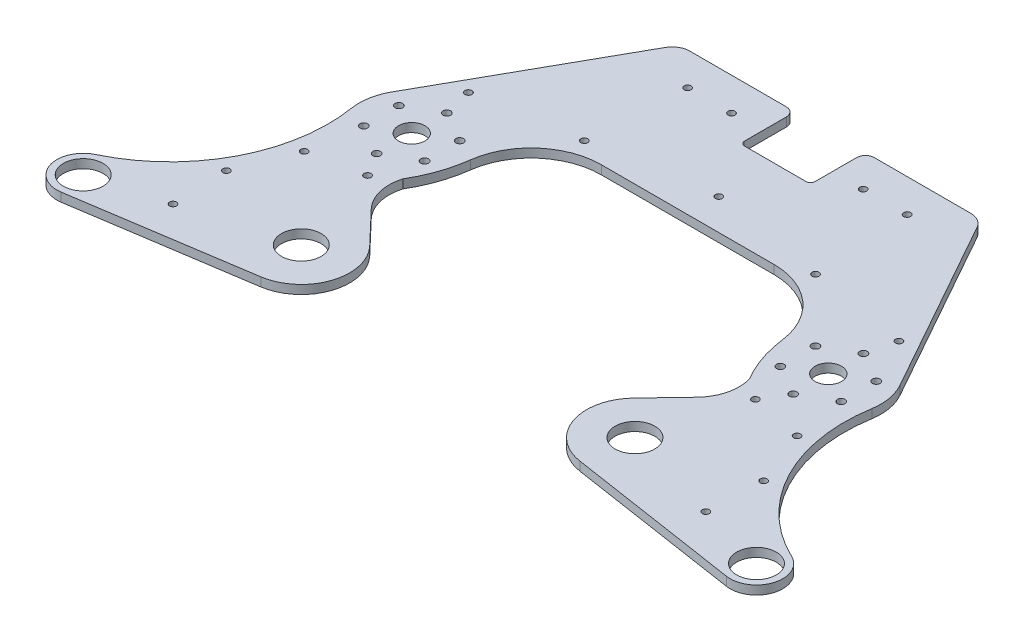
SolidWorks part; units mm, degrees
other "Marca1"
sketch "Croquis4" plane through (-508, 6.35, -221.5657) normal (0, 1, 0) x (1, 0, 0)
sketch "Croquis5" plane through (-262.5313, 6.35, -249.2375) normal (0, 1, 0) x (1, 0, 0)
sketch "Croquis6" plane through (-161.9393, 4.5, -121.1622) normal (0, 1, 0) x (1, 0, 0)
sketch "Croquis7" plane through (-262.5313, 6.35, -249.2375) normal (0, 1, 0) x (1, 0, 0)
sketch "Croquis9" plane through (-161.9393, 10.85, -121.1622) normal (0, 1, 0) x (1, 0, 0)
sketch "Croquis10" plane through (-262.5313, 6.35, -249.2375) normal (0, 1, 0) x (1, 0, 0)
sketch "Croquis12" plane through (-264.3199, 10.85, -20.8386) normal (0, 1, 0) x (1, 0, 0)
sketch "Croquis15" plane through (-262.5313, 6.35, -249.2375) normal (0, 1, 0) x (1, 0, 0)
sketch "Croquis16" plane through (-262.5313, 6.35, -249.2375) normal (0, 1, 0) x (1, 0, 0)
sketch "Croquis17" plane through (-262.5313, 6.35, -249.2375) normal (0, 1, 0) x (1, 0, 0)
sketch "Croquis18" plane through (-262.5313, 6.35, -249.2375) normal (0, 1, 0) x (1, 0, 0)
sketch "Croquis19" [suppressed] plane through (-264.3199, 10.85, -20.8386) normal (0, 1, 0) x (1, 0, 0)
sketch "Croquis20" [suppressed] plane through (-161.9393, 10.85, -121.1622) normal (0, 1, 0) x (1, 0, 0)
sketch "Croquis21" plane through (-264.3199, 10.85, -20.8386) normal (0, 1, 0) x (1, 0, 0)
sketch "Croquis22" plane through (-262.5313, 6.35, -249.2375) normal (0, 1, 0) x (1, 0, 0)
material "Acrílico (Impacto medio-alto)"
ref_plane "Alzado" through (0, 0, 0) normal (0, 0, 1) x (1, 0, 0)
ref_plane "Planta" through (0, 0, 0) normal (0, 1, 0) x (1, 0, 0)
ref_plane "Vista lateral" through (0, 0, 0) normal (1, 0, 0) x (0, 0, -1)
sketch "Dibujo" plane through (0, 0, 0) normal (0, 1, 0) x (1, 0, 0)
  line L0 (0, 0) -> (0, 158.75) construction
  line L1 (0, 158.75) -> (-508, 158.75) construction
  line L2 (-125.8733, 18.3704) -> (-248.7046, -16.5546) construction
  line L3 (-238.258, -53.2954) -> (-115.4267, -18.3704) construction
  line L4 (-160.1534, 108.938) -> (-149.1603, -2.8048) construction
  line L5 (-141.9901, 113.8973) -> (-94.6704, 12.0732) construction
  circle A0 centre (-120.65, 0) radius 50.8
  circle A1 centre (-243.4813, -34.925) radius 28.575
  arc A2 (-248.7046, -16.5546) -> (-238.258, -53.2954) centre (-243.4813, -34.925) ccw construction
  arc A3 (-115.4267, -18.3704) -> (-125.8733, 18.3704) centre (-120.65, 0) ccw construction
  circle A4 centre (-150.65, 109.8729) radius 30
  arc A5 (-141.9901, 113.8973) -> (-160.1534, 108.938) centre (-150.65, 109.8729) ccw construction
  arc A6 (-149.1603, -2.8048) -> (-94.6704, 12.0732) centre (-120.65, 0) ccw construction
  dimension "D1" = 101.6
  dimension "D5" = 57.15
  dimension "D6" = 38.1972
  dimension "D9" = 60
  dimension "D10" = 19.0986
  dimension "D11" = 57.2958
  dimension "D2" = 241.3
  dimension "D3" = 508
  dimension "D4" = 107.95
  dimension "D8" = 34.925
  dimension "D13" = 241.3
sketch "Croquis2" plane through (0, 0, 0) normal (0, 1, 0) x (1, 0, 0)
  line L0 (-240.6004, -53.7559) -> (-115.3574, -34.5954)
  line L1 (-183.8248, 128.4595) -> (-112.6796, 255.445)
  line L2 (-101.6, 261.9375) -> (101.6, 261.9375)
  line L3 (0, 287.155) -> (0, -59.1328) construction
  line L4 (183.8248, 128.4595) -> (112.6796, 255.445)
  line L5 (240.6004, -53.7559) -> (115.3574, -34.5954)
  line L6 (-95.3203, 24.1508) -> (-117.9194, 47.853)
  line L7 (-141.9901, 113.8973) -> (-94.6704, 12.0732) construction
  line L8 (0, 158.75) -> (-508, 158.75) construction
  line L9 (-62.4132, 158.75) -> (62.4132, 158.75)
  line L10 (95.3203, 24.1508) -> (117.9194, 47.853)
  line L12 (0, 158.75) -> (0, -117.475) construction
  line L13 (-117.475, -117.475) -> (117.475, -117.475) construction
  line L14 (-117.475, -117.475) -> (-117.475, 117.475) construction
  line L15 (-117.475, 117.475) -> (117.475, 117.475) construction
  line L16 (117.475, -117.475) -> (117.475, 117.475) construction
  line L17 (-117.475, -117.475) -> (117.475, 117.475) construction
  line L18 (-117.475, 117.475) -> (117.475, -117.475) construction
  line L20 (-25.4381, 261.9375) -> (25.4381, 261.9375)
  line L21 (-25.4381, 261.9375) -> (-25.4381, 222.25)
  line L22 (-25.4381, 222.25) -> (25.4381, 222.25)
  line L23 (25.4381, 261.9375) -> (25.4381, 222.25)
  line L24 (-25.4381, 261.9375) -> (25.4381, 222.25) construction
  line L25 (-25.4381, 222.25) -> (25.4381, 261.9375) construction
  circle A0 centre (-243.4813, -34.925) radius 14.3256
  circle A1 centre (-120.65, 0) radius 14.3256
  circle A3 centre (-243.4813, -34.925) radius 19.05
  circle A4 centre (-120.65, 0) radius 34.9979
  arc A6 (-149.1603, -2.8048) -> (-94.6704, 12.0732) centre (-120.65, 0) ccw construction
  arc A7 (-188.1821, 103.7596) -> (-251.6976, -17.7379) centre (-300.9954, 85.3844) cw
  arc A8 (-112.6796, 255.445) -> (-101.6, 261.9375) centre (-101.6, 249.2375) cw
  arc A10 (-117.9194, 47.853) -> (-125.3591, 78.1101) centre (-95.246, 69.4712) cw
  arc A11 (112.6796, 255.445) -> (101.6, 261.9375) centre (101.6, 249.2375) ccw
  arc A12 (188.1821, 103.7596) -> (251.6976, -17.7379) centre (300.9954, 85.3844) ccw
  arc A13 (-112.7986, 114.4272) -> (-62.4132, 158.75) centre (-62.4132, 107.95) cw
  arc A14 (183.8248, 128.4595) -> (188.1821, 103.7596) centre (150.65, 109.8729) cw
  circle A15 centre (120.65, 0) radius 34.9979
  circle A16 centre (243.4813, -34.925) radius 19.05
  circle A17 centre (150.65, 109.8729) radius 9.5631
  circle A18 centre (120.65, 0) radius 14.3256
  circle A19 centre (243.4813, -34.925) radius 14.3256
  circle A20 centre (-150.65, 109.8729) radius 25.4 construction
  circle A21 centre (-150.65, 135.2729) radius 2.75
  circle A22 centre (-128.653, 122.5729) radius 2.75
  circle A23 centre (-128.653, 97.1729) radius 2.75
  circle A24 centre (-150.65, 84.4729) radius 2.75
  circle A25 centre (-172.647, 97.1729) radius 2.75
  circle A26 centre (-172.647, 122.5729) radius 2.75
  circle A27 centre (150.65, 109.8729) radius 25.4 construction
  circle A28 centre (172.647, 122.5729) radius 2.75
  circle A29 centre (172.647, 97.1729) radius 2.75
  circle A30 centre (150.65, 84.4729) radius 2.75
  circle A31 centre (128.653, 97.1729) radius 2.75
  circle A32 centre (128.653, 122.5729) radius 2.75
  circle A33 centre (150.65, 135.2729) radius 2.75
  arc A35 (-183.8248, 128.4595) -> (-188.1821, 103.7596) centre (-150.65, 109.8729) ccw
  arc A36 (112.7986, 114.4272) -> (62.4132, 158.75) centre (62.4132, 107.95) ccw
  arc A37 (125.3591, 78.1101) -> (112.7986, 114.4272) centre (206.3577, 126.4546) cw
  circle A39 centre (-150.65, 109.8729) radius 9.5631
  circle A40 centre (-120.65, 0) radius 50.8 construction
  circle A41 centre (-150.65, 109.8729) radius 36.35 construction
  arc A42 (117.9194, 47.853) -> (125.3591, 78.1101) centre (95.246, 69.4712) ccw
  circle A43 centre (-150.65, 109.8729) radius 30 construction
  arc A44 (-125.3591, 78.1101) -> (-112.7986, 114.4272) centre (-206.3577, 126.4546) ccw
  point P53 (0, 261.9375)
  point P71 (-150.65, 109.8729)
  point P88 (-117.2099, 95.6223)
  point P89 (150.65, 109.8729)
  point P93 (0, 158.75)
  point P97 (0, 0)
  point P104 (0, 242.0938)
  dimension "D1" = 28.6512
  dimension "D2" = 6.35
  dimension "D3" = 6.35
  dimension "D4" = 38.1
  dimension "D5" = 114.3
  dimension "D6" = 31.3278
  dimension "D7" = 32.7493
  dimension "D9" = 12.7
  dimension "D11" = 50.8
  dimension "D12" = 5.5
  dimension "D10" = 50.8
  dimension "D14" = 234.95
  dimension "D15" = 94.329
  dimension "D16" = 6.2059
  dimension "D17" = 34.4369
  dimension "D21" = 19.1262
  dimension "D8" = 203.2
  dimension "D18" = 50.8762
  dimension "D19" = 39.6875
  dimension "D20" = 63.5
  dimension "D13" = 6
extrude "Saliente-Extruir1" add sketch "Croquis2" along normal blind 6.35 contours A15 L5 A16 A12 A14 L4 A11 L2 A8 L1 A35 A7 A3 L0 A4 A32 A30 A28 A26 A25 A24 A23 A22 A21 A39 A17 A29 A31 A33 | A15 A18 | A16 A19 | A4 A1 | A3 A0 | L23 L2 L21 L22 | A39 | A25 | A26 | A22 | A23 | A24 | A21 | A17 | A33 | A32 | A28 | A31 | A30 | A29 region at (-224.5201, 0, 51.206) region at (-261.1719, 0, 40.3755) region at (-152.8373, 0, -10.9784) region at (0, 0, -242.0938) region at (133.2892, 0, -31.5721) region at (259.1411, 0, 25.054) region at (150.65, 0, -109.8729) region at (-150.65, 0, -135.2729) region at (-128.653, 0, -122.5729) region at (-128.653, 0, -97.1729) region at (-150.65, 0, -84.4729) region at (-172.647, 0, -97.1729) region at (-172.647, 0, -122.5729) region at (172.647, 0, -122.5729) region at (172.647, 0, -97.1729) region at (150.65, 0, -84.4729) region at (128.653, 0, -97.1729) region at (128.653, 0, -122.5729) region at (150.65, 0, -135.2729) region at (-150.65, 0, -109.8729)
extrude "Cortar-Extruir1" cut sketch "Croquis2<4>" along normal through all contours L23 L2 L21 L22 | A17 | A29 | A30 | A31 | A32 | A33 | A28 | A39 | A26 | A21 | A22 | A23 | A25 | A24 region at (0, 0, -242.0938) region at (150.65, 0, -109.8729) region at (-150.65, 0, -135.2729) region at (-128.653, 0, -122.5729) region at (-128.653, 0, -97.1729) region at (-150.65, 0, -84.4729) region at (-172.647, 0, -97.1729) region at (-172.647, 0, -122.5729) region at (172.647, 0, -122.5729) region at (172.647, 0, -97.1729) region at (150.65, 0, -84.4729) region at (128.653, 0, -97.1729) region at (128.653, 0, -122.5729) region at (150.65, 0, -135.2729) region at (-150.65, 0, -109.8729)
sketch "Croquis2<4>" plane through (0, 0, 0) normal (0, 1, 0) x (1, 0, 0) same geometry as "Croquis2"
sketch "Croquis14" plane through (0, 6.35, 0) normal (0, 1, 0) x (1, 0, 0)
  line L0 (-240.6004, -53.7559) -> (-115.3574, -34.5954) construction
  line L1 (-101.6, 261.9375) -> (-25.4381, 261.9375) construction
  line L2 (-25.4381, 261.9375) -> (-25.4381, 222.25) construction
  line L5 (0, 158.75) -> (-508, 158.75) construction
  line L7 (-183.8248, 128.4595) -> (-112.6796, 255.445) construction
  line L9 (-62.4132, 158.75) -> (62.4132, 158.75) construction
  line L11 (25.4381, 261.9375) -> (25.4381, 222.25) construction
  line L12 (0, 0) -> (0, 222.25) construction
  line L13 (-25.4381, 222.25) -> (25.4381, 222.25) construction
  circle A0 centre (-192.6813, -20.7294) radius 4.7625
  circle A1 centre (-192.6813, -20.7294) radius 2.4892
  circle A2 centre (-243.4813, -34.925) radius 28.575 construction
  circle A5 centre (-194.31, 19.4563) radius 4.7625
  circle A6 centre (-194.31, 19.4563) radius 2.4892
  circle A7 centre (-178.2433, 59.69) radius 4.7625
  circle A8 centre (-178.2433, 59.69) radius 2.4892
  arc A9 (-251.6976, -17.7379) -> (-188.1821, 103.7596) centre (-300.9954, 85.3844) ccw construction
  circle A10 centre (-47.625, 238.125) radius 4.7625
  circle A11 centre (-47.625, 238.125) radius 2.4892
  circle A12 centre (-79.375, 238.125) radius 4.7625
  circle A13 centre (-79.375, 238.125) radius 2.4892
  circle A14 centre (-120.65, 0) radius 50.8 construction
  circle A15 centre (-140.2263, 67.4904) radius 4.7625
  circle A16 centre (-140.2263, 67.4904) radius 2.4892
  circle A17 centre (47.625, 238.125) radius 2.4892
  circle A18 centre (47.625, 238.125) radius 4.7625
  arc A19 (-125.3591, 78.1101) -> (-117.9194, 47.853) centre (-95.246, 69.4712) ccw construction
  circle A20 centre (79.375, 238.125) radius 2.4892
  circle A21 centre (-150.65, 109.8729) radius 30 construction
  circle A22 centre (0, 181.2925) radius 4.7625
  circle A23 centre (0, 181.2925) radius 2.4892
  circle A24 centre (-83.6274, 167.64) radius 4.7625
  circle A25 centre (-83.6274, 167.64) radius 2.4892
  circle A26 centre (-155.7049, 155.9148) radius 4.7625
  circle A27 centre (-155.7049, 155.9148) radius 2.4892
  circle A28 centre (192.6813, -20.7294) radius 2.4892
  circle A29 centre (192.6813, -20.7294) radius 4.7625
  circle A30 centre (194.31, 19.4563) radius 2.4892
  circle A31 centre (194.31, 19.4563) radius 4.7625
  circle A32 centre (178.2433, 59.69) radius 2.4892
  circle A33 centre (178.2433, 59.69) radius 4.7625
  circle A34 centre (140.2263, 67.4904) radius 2.4892
  circle A35 centre (140.2263, 67.4904) radius 4.7625
  circle A36 centre (83.6274, 167.64) radius 2.4892
  circle A37 centre (83.6274, 167.64) radius 4.7625
  circle A38 centre (155.7049, 155.9148) radius 2.4892
  circle A39 centre (155.7049, 155.9148) radius 4.7625
  circle A40 centre (79.375, 238.125) radius 4.7625
  dimension "D1" = 9.525
  dimension "D2" = 4.9784
  dimension "D3" = 25.4
  dimension "D4" = 50.8
  dimension "D5" = 6.35
  dimension "D6" = 6.35
  dimension "D7" = 8.89
  dimension "D8" = 73.66
  dimension "D9" = 8.89
  dimension "D10" = 7.62
  dimension "D11" = 8.89
  dimension "D12" = 63.5
  dimension "D13" = 17.78
  dimension "D14" = 20.6756
  dimension "D15" = 63.5
  dimension "D16" = 6.35
  dimension "D17" = 23.8125
  dimension "D18" = 22.1869
  dimension "D19" = 31.75
extrude "Cortar-Extruir2" cut sketch "Croquis14" against normal through all contours A1 | A6 | A8 | A16 | A27 | A25 | A23 L12 | L12 A23 | A36 | A38 | A34 | A32 | A30 | A28 | A13 | A11 | A17 | A20 region at (-1.0564, 6.35, -181.2925) region at (1.0564, 6.35, -181.2925) region at (-192.6813, 6.35, 20.7294) region at (-194.31, 6.35, -19.4563) region at (-178.2433, 6.35, -59.69) region at (-47.625, 6.35, -238.125) region at (-79.375, 6.35, -238.125) region at (-140.2263, 6.35, -67.4904) region at (47.625, 6.35, -238.125) region at (79.375, 6.35, -238.125) region at (-83.6274, 6.35, -167.64) region at (-155.7049, 6.35, -155.9148) region at (192.6813, 6.35, 20.7294) region at (194.31, 6.35, -19.4563) region at (178.2433, 6.35, -59.69) region at (140.2263, 6.35, -67.4904) region at (83.6274, 6.35, -167.64) region at (155.7049, 6.35, -155.9148)
fillet "Redondeo1" radius 6.35 2 edges at (25.4381, 3.175, -261.9375) (-25.4381, 3.175, -261.9375)
fillet "Redondeo2" radius 3.175 2 edges at (-25.4381, 3.175, -222.25) (25.4381, 3.175, -222.25)
sketch "Croquis8" [suppressed] plane through (0, 6.35, 0) normal (0, 1, 0) x (1, 0, 0)
  line L0 (-141.9901, 113.8973) -> (-94.6704, 12.0732) construction
  line L1 (-160.1534, 108.938) -> (-149.1603, -2.8048) construction
  line L2 (-141.9901, 113.8973) -> (-94.6704, 12.0732) construction
  line L3 (-160.1534, 108.938) -> (-149.1603, -2.8048) construction
  line L4 (-158.1033, 109.1397) -> (-147.1102, -2.6031)
  line L5 (-143.8583, 113.0292) -> (-96.5386, 11.2051)
  line L6 (-161.8851, 108.7676) -> (-150.8919, -2.9752)
  line L7 (-140.4122, 114.6306) -> (-93.0925, 12.8065)
  arc A0 (-141.9901, 113.8973) -> (-160.1534, 108.938) centre (-150.65, 109.8729) ccw construction
  arc A1 (-149.1603, -2.8048) -> (-94.6704, 12.0732) centre (-120.65, 0) ccw construction
  arc A2 (-141.9901, 113.8973) -> (-160.1534, 108.938) centre (-150.65, 109.8729) ccw construction
  arc A3 (-149.1603, -2.8048) -> (-94.6704, 12.0732) centre (-120.65, 0) ccw construction
  arc A4 (-147.1102, -2.6031) -> (-96.5386, 11.2051) centre (-120.65, 0) ccw
  arc A5 (-143.8583, 113.0292) -> (-158.1033, 109.1397) centre (-150.65, 109.8729) ccw
  arc A6 (-150.8919, -2.9752) -> (-93.0925, 12.8065) centre (-120.65, 0) ccw
  arc A7 (-140.4122, 114.6306) -> (-161.8851, 108.7676) centre (-150.65, 109.8729) ccw
  dimension "D1" = 2.06
  dimension "D2" = 3.8
extrude "Saliente-Extruir2" [suppressed] add sketch "Croquis8" along normal mid plane 9 separate body
delete or keep bodies "Sólido-Eliminar/Conservar 1" [suppressed] type delete bodies bodies 106
sketch "Croquis11" [suppressed] plane through (0, 6.35, 0) normal (0, 1, 0) x (1, 0, 0)
  line L0 (-238.258, -53.2954) -> (-115.4267, -18.3704) construction
  line L1 (-125.8733, 18.3704) -> (-248.7046, -16.5546) construction
  line L2 (-238.258, -53.2954) -> (-115.4267, -18.3704) construction
  line L3 (-125.8733, 18.3704) -> (-248.7046, -16.5546) construction
  line L4 (-125.3099, 16.389) -> (-248.1413, -18.536)
  line L5 (-238.8214, -51.314) -> (-115.9901, -16.389)
  line L6 (-126.3492, 20.0441) -> (-249.1805, -14.8809)
  line L7 (-237.7821, -54.9691) -> (-114.9508, -20.0441)
  arc A0 (-115.4267, -18.3704) -> (-125.8733, 18.3704) centre (-120.65, 0) ccw construction
  arc A1 (-248.7046, -16.5546) -> (-238.258, -53.2954) centre (-243.4813, -34.925) ccw construction
  arc A2 (-115.4267, -18.3704) -> (-125.8733, 18.3704) centre (-120.65, 0) ccw construction
  arc A3 (-248.7046, -16.5546) -> (-238.258, -53.2954) centre (-243.4813, -34.925) ccw construction
  arc A4 (-248.1413, -18.536) -> (-238.8214, -51.314) centre (-243.4813, -34.925) ccw
  arc A5 (-115.9901, -16.389) -> (-125.3099, 16.389) centre (-120.65, 0) ccw
  arc A6 (-249.1805, -14.8809) -> (-237.7821, -54.9691) centre (-243.4813, -34.925) ccw
  arc A7 (-114.9508, -20.0441) -> (-126.3492, 20.0441) centre (-120.65, 0) ccw
  dimension "D1" = 2.06
  dimension "D2" = 3.8
extrude "Saliente-Extruir3" [suppressed] add sketch "Croquis11" along normal mid plane 9 separate body
delete or keep bodies "Sólido-Eliminar/Conservar 2" [suppressed] type delete bodies bodies 106
equation "\"D7@Dibujo\" =  ( 70 * 5mm )  + 1"
equation "\"D10@Dibujo\" = 12 * 5mm / pi"
equation "\"D11@Dibujo\" = 36 * 5mm / pi"
equation "\"D12@Dibujo\" =  ( 70 * 5mm )  + 1mm"
